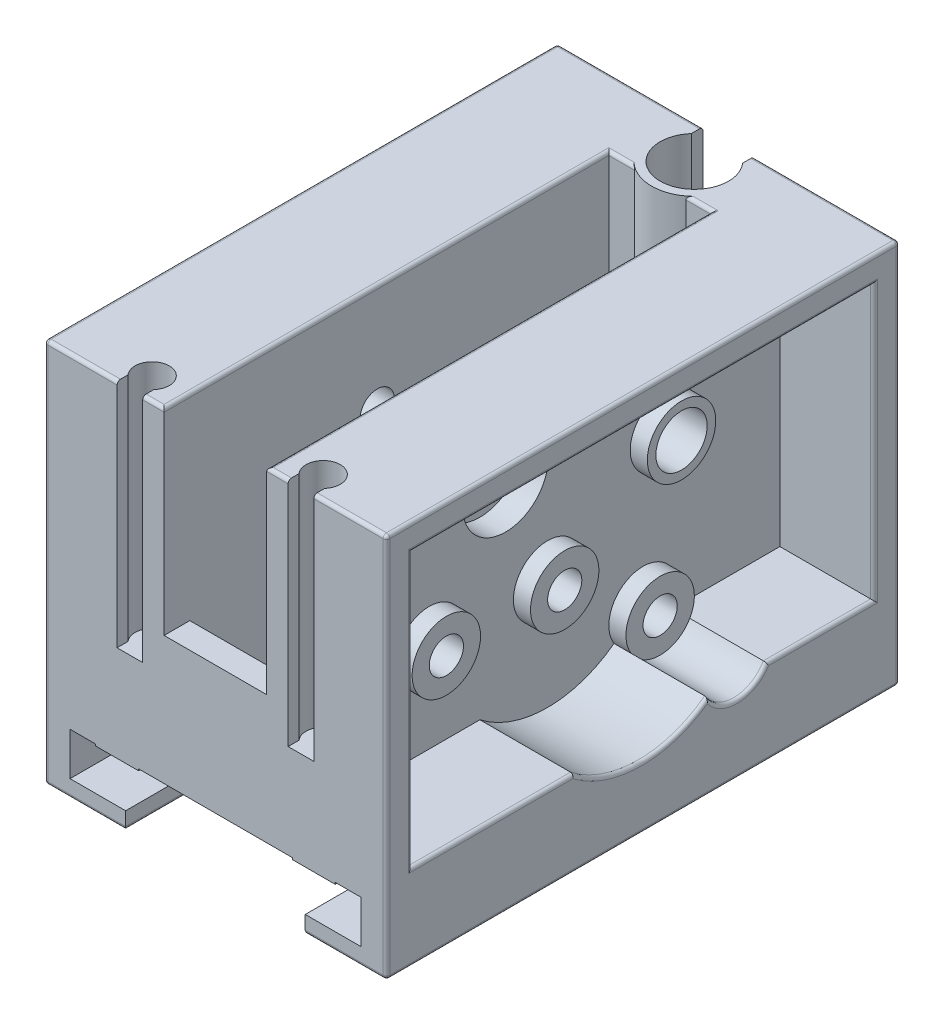
SolidWorks part; units mm, degrees
ref_plane "前视基准面" through (0, 0, 0) normal (0, 0, 1) x (1, 0, 0)
ref_plane "上视基准面" through (0, 0, 0) normal (0, 1, 0) x (1, 0, 0)
ref_plane "右视基准面" through (0, 0, 0) normal (1, 0, 0) x (0, 0, -1)
sketch "草图1" plane through (0, 0, 0) normal (0, 0, 1) x (1, 0, 0)
  line L1 (-10, 0) -> (10, 0)
  line L2 (-10, 0) -> (-10, 22.5)
  line L3 (-10, 22.5) -> (10, 22.5)
  line L4 (10, 0) -> (10, 22.5)
extrude "凸台-拉伸1" add sketch "草图1" against normal blind 30
sketch "草图2" plane through (0, 0, 0) normal (0, 0, 1) x (1, 0, 0)
  line L0 (-10, 0) -> (10, 0) construction
  line L1 (-5.25, 0) -> (5.25, 0)
  line L2 (-5.25, 0) -> (-5.25, 1)
  line L3 (5.25, 1) -> (8.5, 1)
  line L4 (5.25, 0) -> (5.25, 1)
  line L6 (-8.5, 1) -> (-5.25, 1)
  line L7 (-8.5, 1) -> (-8.5, 3.5)
  line L8 (-8.5, 3.5) -> (8.5, 3.5)
  line L9 (8.5, 1) -> (8.5, 3.5)
extrude "切除-拉伸1" cut sketch "草图2" against normal through all
sketch "草图3" plane through (0, 22.5, 0) normal (0, 1, 0) x (-1, 0, 0)
  line L0 (-1.5, -26) -> (-3, -26)
  line L1 (3, -1.5) -> (-3, -1.5)
  line L2 (3, -1.5) -> (3, -26)
  line L3 (3, -26) -> (1.5, -26)
  line L4 (-3, -1.5) -> (-3, -26)
  arc A0 (1.5, -26) -> (-1.5, -26) centre (0, -28) ccw
extrude "切除-拉伸2" cut sketch "草图3" against normal blind 18.5
sketch "草图4" plane through (0, 22.5, 0) normal (0, 1, 0) x (-1, 0, 0)
  line L0 (-10, -30) -> (10, -30) construction
  line L1 (1.5, -30) -> (-1.5, -30)
  line L2 (1.5, -30) -> (1.5, -29.3229)
  line L4 (-1.5, -30) -> (-1.5, -29.3229)
  arc A0 (1.5, -29.3229) -> (-1.5, -29.3229) centre (0, -28) ccw
extrude "切除-拉伸3" cut sketch "草图4" against normal blind 17
sketch "草图5" plane through (0, 22.5, 0) normal (0, 1, 0) x (-1, 0, 0)
  line L0 (-10, 0) -> (10, 0) construction
  line L1 (3, -1.5) -> (-3, -1.5)
  line L2 (3, -1.5) -> (3, 0)
  line L3 (3, 0) -> (-3, 0)
  line L4 (-3, -1.5) -> (-3, 0)
extrude "切除-拉伸4" cut sketch "草图5" against normal blind 11.5
sketch "草图6" plane through (0, 22.5, 0) normal (0, 1, 0) x (-1, 0, 0)
  line L0 (3, 0) -> (10, 0) construction
  line L1 (5.75, 0) -> (4.25, 0)
  line L2 (5.75, 0) -> (5.75, -0.6386)
  line L3 (-10, 0) -> (-3, 0) construction
  line L4 (4.25, 0) -> (4.25, -0.6386)
  line L5 (-4.25, 0) -> (-5.75, 0)
  line L6 (-4.25, 0) -> (-4.25, -0.6386)
  line L8 (-5.75, 0) -> (-5.75, -0.6386)
  arc A0 (4.25, -0.6386) -> (5.75, -0.6386) centre (5, -1.3) ccw
  arc A1 (-5.75, -0.6386) -> (-4.25, -0.6386) centre (-5, -1.3) ccw
extrude "切除-拉伸5" cut sketch "草图6" against normal blind 13.5
sketch "草图7" plane through (0, 3.5, 0) normal (0, -1, 0) x (1, 0, 0)
  line L0 (-10, -30) -> (-5.25, -30) construction
  line L1 (-7, -30) -> (-4.5, -30)
  line L2 (-7, -30) -> (-7, 0)
  line L3 (-7, 0) -> (-4.5, 0)
  line L4 (-4.5, -30) -> (-4.5, 0)
  line L5 (8.5, 0) -> (-8.5, 0) construction
  line L6 (8.5, -30) -> (-8.5, -30) construction
  line L7 (4.5, -30) -> (7, -30)
  line L8 (4.5, -30) -> (4.5, 0)
  line L9 (4.5, 0) -> (7, 0)
  line L10 (7, -30) -> (7, 0)
  line L11 (5.25, 0) -> (10, 0) construction
extrude "凸台-拉伸2" add sketch "草图7" along normal blind 0.1
sketch "草图8" plane through (0, 4, 0) normal (0, 1, 0) x (-1, 0, 0)
  line L1 (3, -26) -> (3, -1.5) construction
  line L2 (3, -25) -> (-3, -25)
  line L3 (3, -25) -> (3, -16)
  line L4 (3, -16) -> (-3, -16)
  line L6 (-3, -25) -> (-3, -16)
  line L7 (-3, -1.5) -> (-3, -26) construction
  line L8 (3, -26) -> (3, 0) construction
extrude "切除-拉伸6" cut sketch "草图8" against normal up to next
sketch "草图9" plane through (-10, 0, 0) normal (-1, 0, 0) x (0, 0, 1)
  line L0 (0, 22.5) -> (0, 0) construction
  circle A0 centre (-20.5, 6) radius 1
  circle A1 centre (-21.75, 14.25) radius 1.5
  circle A2 centre (-14.92, 10.09) radius 1
  circle A3 centre (-8, 10.22) radius 1
  circle A4 centre (-12.46, 16.25) radius 1
  dimension "D1" = 21.75
  dimension "D2" = 20.5
  dimension "D3" = 14.92
  dimension "D4" = 8
  dimension "D5" = 12.46
extrude "切除-拉伸7" cut sketch "草图9" against normal through all
sketch "草图11" plane through (-10, 0, 0) normal (-1, 0, 0) x (0, 0, 1)
  line L0 (-18.7679, 5) -> (-1.5, 5)
  line L2 (-1.5, 5) -> (-1.5, 21)
  line L3 (-1.5, 21) -> (-28.5, 21)
  line L4 (-28.5, 5) -> (-28.5, 21)
  line L5 (-28.5, 5) -> (-22.2321, 5)
  arc A0 (-22.2321, 5) -> (-18.7679, 5) centre (-20.5, 6) ccw
extrude "切除-拉伸9" cut sketch "草图11" against normal blind 5.5
sketch "草图12" plane through (10, 0, 0) normal (1, 0, 0) x (0, 0, -1)
  circle A0 centre (12.46, 16.25) radius 2.5
extrude "切除-拉伸10" cut sketch "草图12" against normal up to next
sketch "草图13" plane through (10, 0, 0) normal (1, 0, 0) x (0, 0, -1)
  line L1 (1.5, 5) -> (10.9584, 5)
  line L2 (1.5, 5) -> (1.5, 21)
  line L3 (1.5, 21) -> (28.5, 21)
  line L4 (28.5, 5) -> (28.5, 21)
  line L5 (22.2321, 5) -> (28.5, 5)
  arc A0 (10.9584, 5) -> (18.8038, 4.9404) centre (14.92, 10.09) ccw
  arc A1 (18.8038, 4.9404) -> (22.2321, 5) centre (20.5, 6) ccw
extrude "切除-拉伸11" cut sketch "草图13" against normal blind 5.5
sketch "草图14" plane through (0, 21, 0) normal (0, -1, 0) x (1, 0, 0)
  line L2 (-5.75, -0.6386) -> (-5.75, -0.3)
  line L4 (-4.25, -0.6386) -> (-4.25, -0.3)
  line L6 (4.25, -0.3) -> (4.25, -0.6386)
  line L8 (5.75, -0.3) -> (5.75, -0.6386)
  arc A0 (4.25, -0.6386) -> (5.75, -0.6386) centre (5, -1.3) ccw
  arc A1 (-5.75, -0.6386) -> (-4.25, -0.6386) centre (-5, -1.3) ccw
  arc A2 (-5.75, -0.3) -> (-4.25, -0.3) centre (-5, -1.3) ccw
  arc A3 (4.25, -0.3) -> (5.75, -0.3) centre (5, -1.3) ccw
extrude "凸台-拉伸3" add sketch "草图14" along normal blind 12.5
sketch "草图15" plane through (0, 8.5, 0) normal (0, 1, 0) x (-1, 0, 0)
  line L1 (-4.5, -1.5) -> (-4.5, -2.166)
  line L2 (-4.5, -1.5) -> (-5.9798, -1.5)
  line L3 (4.5, -1.5) -> (5.9798, -1.5)
  line L6 (4.5, -1.5) -> (4.5, -2.166)
  arc A0 (4.5, -2.166) -> (5.9798, -1.5) centre (5, -1.3) ccw
  arc A1 (-5.9798, -1.5) -> (-4.5, -2.166) centre (-5, -1.3) ccw
  arc M19 (-5.9798, -1.5) -> (-4.5, -2.166) centre (-5, -1.3) ccw
extrude "凸台-拉伸4" add sketch "草图15" along normal up to surface (0.5 mm away) contours L2 L1 M19 | A0 L6 L3 region at (5.148, 8.5, -1.852) region at (-5.148, 8.5, -1.852) up to face at (-4.9599, 9, -0.9251)
sketch "草图16" plane through (-4.5, 0, 0) normal (-1, 0, 0) x (0, 0, 1)
  circle A0 centre (-21.75, 14.25) radius 2
  circle A1 centre (-14.92, 10.09) radius 2
  circle A2 centre (-12.46, 16.25) radius 2
  circle A3 centre (-8, 10.22) radius 2
  circle A4 centre (-20.5, 6) radius 2
  circle A5 centre (-21.75, 14.25) radius 1.5
  circle A6 centre (-20.5, 6) radius 1
  circle A7 centre (-14.92, 10.09) radius 1
  circle A8 centre (-12.46, 16.25) radius 1
  circle A9 centre (-8, 10.22) radius 1
extrude "凸台-拉伸5" add sketch "草图16" along normal blind 1
sketch "草图17" plane through (4.5, 0, 0) normal (1, 0, 0) x (0, 0, -1)
  circle A0 centre (8, 10.22) radius 1
  circle A1 centre (8, 10.22) radius 2
  circle A2 centre (14.92, 10.09) radius 1
  circle A3 centre (14.92, 10.09) radius 2
  circle A4 centre (21.75, 14.25) radius 1.5
  circle A5 centre (21.75, 14.25) radius 2
  circle A6 centre (20.5, 6) radius 1
  circle A7 centre (20.5, 6) radius 2
extrude "凸台-拉伸6" add sketch "草图17" along normal blind 1
fillet "圆角1" radius 0.2 27 edges at (7.625, 0, 0) (7.625, 0, -30) (5.25, 0, -15) (-7.625, 0, -30) (-7.625, 0, 0) (-5.25, 0, -15) (-10, 0, -15) (-10, 11.25, -30) (-10, 22.5, -15) (-10, 11.25, 0) (-10, 21, -15) (-10, 13, -28.5) (-10, 5, -25.366) (-10, 4, -20.5) (-10, 5, -10.134) (-10, 13, -1.5) (10, 22.5, -15) (10, 11.25, -30) (10, 0, -15) (10, 11.25, 0) (10, 5, -6.2292) (10, 3.6402, -14.871) (10, 4.0003, -20.5348) (10, 5, -25.366) (10, 13, -28.5) (10, 21, -15) (10, 13, -1.5)
fillet "圆角2" radius 0.2 14 edges at (-9.9414, 22.4414, -29.9414) (9.9414, 22.4414, -29.9414) (9.9414, 22.4414, -0.0586) (-9.9414, 22.4414, -0.0586) (-5.65, 22.5, -30) (5.65, 22.5, -30) (2.25, 22.5, -26) (-2.25, 22.5, -26) (-3, 22.5, -13) (3, 22.5, -13) (7.775, 22.5, 0) (3.625, 22.5, 0) (-3.625, 22.5, 0) (-7.775, 22.5, 0)
